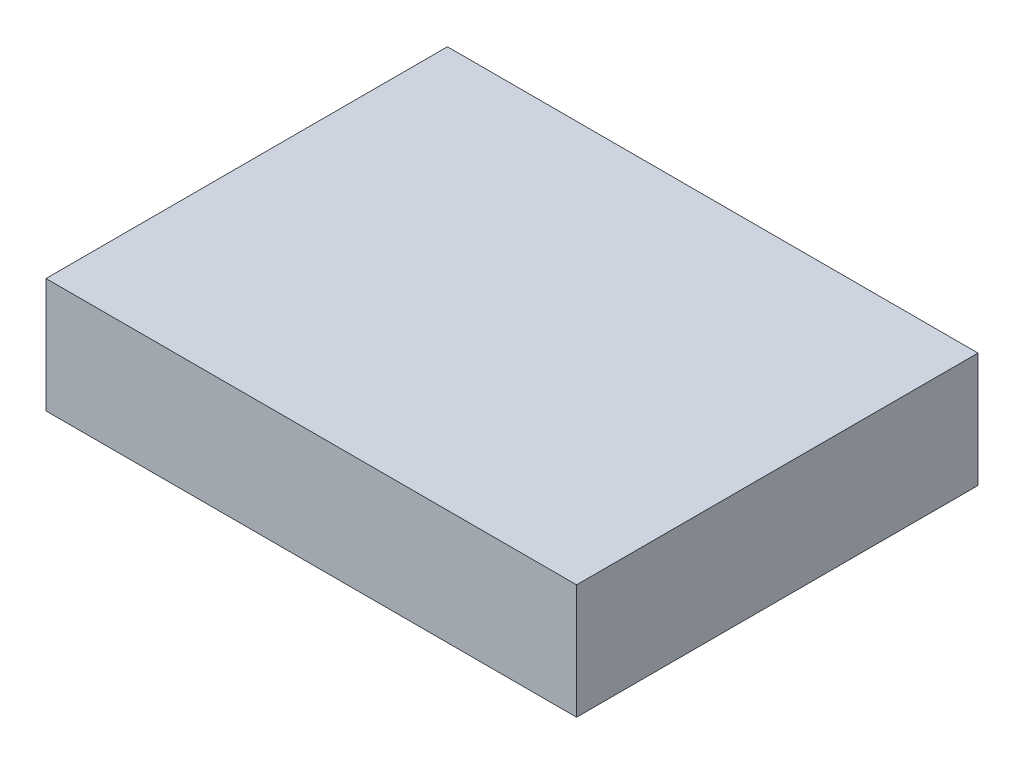
SolidWorks part; units mm, degrees
ref_plane "Front Plane" through (0, 0, 0) normal (0, 0, 1) x (1, 0, 0)
ref_plane "Top Plane" through (0, 0, 0) normal (0, 1, 0) x (1, 0, 0)
ref_plane "Right Plane" through (0, 0, 0) normal (1, 0, 0) x (0, 0, -1)
sketch "Sketch1" plane through (0, 0, 0) normal (0, 1, 0) x (1, 0, 0)
  line L1 (-23.5, -17.78) -> (23.5, -17.78)
  line L2 (-23.5, -17.78) -> (-23.5, 17.78)
  line L3 (-23.5, 17.78) -> (23.5, 17.78)
  line L4 (23.5, -17.78) -> (23.5, 17.78)
  line L5 (-23.5, -17.78) -> (23.5, 17.78) construction
  line L6 (-23.5, 17.78) -> (23.5, -17.78) construction
  point P0 (0, 0)
  dimension "D1" = 47
  dimension "D2" = 35.56
extrude "Boss-Extrude1" add sketch "Sketch1" along normal blind 10.16
